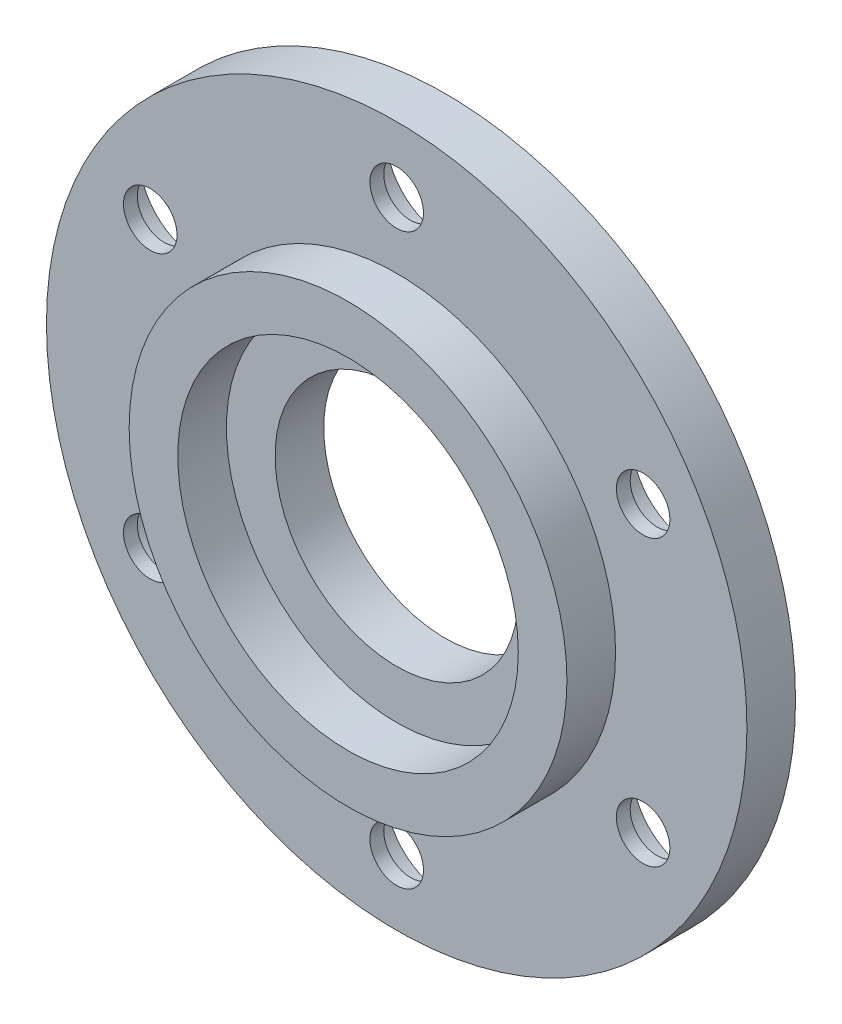
SolidWorks part; units mm, degrees
material "6061-T6 (SS)"
ref_plane "Front Plane" through (0, 0, 0) normal (0, 0, 1) x (1, 0, 0)
ref_plane "Top Plane" through (0, 0, 0) normal (0, 1, 0) x (1, 0, 0)
ref_plane "Right Plane" through (0, 0, 0) normal (1, 0, 0) x (0, 0, -1)
sketch "Sketch Spindle Skeleton" plane through (0, 0, 0) normal (1, 0, 0) x (0, 0, -1)
  line L0 (-109.9, -9.5) -> (-134, -9.5)
  line L5 (-1000, 0) -> (49000, 0)
  line L6 (0, -9.5) -> (0, 9.5)
  line L13 (0, 9.5) -> (-48.3, 9.5)
  line L26 (-48.3, 9.5) -> (-48.3, 14)
  line L27 (-48.3, 14) -> (-109.9, 14)
  line L32 (-109.9, 14) -> (-109.9, 9.5)
  line L34 (-150, 7) -> (-150, -7)
  line L36 (-109.9, -9.5) -> (-109.9, -14)
  line L37 (-109.9, -14) -> (-48.3, -14)
  line L38 (-48.3, -14) -> (-48.3, -9.5)
  line L39 (0, -9.5) -> (-48.3, -9.5)
  line L40 (-24.2, 36) -> (-19.2, 36)
  line L41 (-126.5, 22.5) -> (-109.9, 22.5)
  line L42 (-126.5, 22.5) -> (-126.5, -22.5)
  line L43 (-126.5, -22.5) -> (-109.9, -22.5)
  line L44 (-109.9, 22.5) -> (-109.9, -22.5)
  line L45 (-126.5, 22.5) -> (-109.9, -22.5) construction
  line L46 (-126.5, -22.5) -> (-109.9, 22.5) construction
  line L47 (-31.7, 22.5) -> (-48.3, 22.5)
  line L48 (-31.7, 22.5) -> (-31.7, -22.5)
  line L49 (-31.7, -22.5) -> (-48.3, -22.5)
  line L50 (-48.3, 22.5) -> (-48.3, -22.5)
  line L51 (-31.7, 22.5) -> (-48.3, -22.5) construction
  line L52 (-31.7, -22.5) -> (-48.3, 22.5) construction
  line L59 (-19.2, 36) -> (-19.2, -36)
  line L60 (-19.2, -36) -> (-24.2, -36)
  line L61 (-24.2, -22.5) -> (-29.2, -22.5)
  line L62 (-29.2, -22.5) -> (-29.2, -17.5)
  line L63 (-29.2, -17.5) -> (-24.2, -17.5)
  line L64 (-24.2, -17.5) -> (-24.2, 17.5)
  line L65 (-24.2, 17.5) -> (-29.2, 17.5)
  line L66 (-29.2, 17.5) -> (-29.2, 22.5)
  line L67 (-29.2, 22.5) -> (-24.2, 22.5)
  line L68 (-24.2, 22.5) -> (-24.2, 36)
  line L69 (-24.2, -22.5) -> (-24.2, -36)
  line L71 (-131.5, 36) -> (-25.2, 36)
  line L72 (-131.5, 36) -> (-131.5, -36)
  line L73 (-131.5, -36) -> (-25.2, -36)
  line L74 (-25.2, 36) -> (-25.2, -36)
  line L75 (-131.5, 36) -> (-25.2, -36) construction
  line L76 (-131.5, -36) -> (-25.2, 36) construction
  line L77 (-134, -9.5) -> (-134, -7)
  line L78 (-134, -7) -> (-150, -7)
  line L79 (-109.9, 9.5) -> (-134, 9.5)
  line L80 (-134, 7) -> (-150, 7)
  line L81 (-134, 9.5) -> (-134, 7)
  line L82 (-121.95, 9.5) -> (-121.95, -9.5) construction
  line L83 (-24.15, 9.5) -> (-24.15, -9.5) construction
  point P3 (0, 0)
  point P18 (-118.2, 0)
  point P24 (-40, 0)
  point P29 (-78.35, 0)
  point P48 (-19.2, 29.25)
revolve "Main Revolve" add sketch "Sketch Spindle Skeleton" angle 360 about L5 region at (0, 22.65, 21.8091) region at (0, 20, 27.2)
sketch "Sketch Center Cut" plane through (0, 0, 24.2) normal (0, 0, 1) x (1, 0, 0)
  circle A0 centre (0, 0) radius 17.5 construction
  circle A1 centre (0, 0) radius 17.5 construction
  circle A2 centre (0, 0) radius 12.5
  dimension "D1" = 5
extrude "Cut Center" cut sketch "Sketch Center Cut" against normal through all
hole_wizard "CBORE for M5 Hex Head Bolt1" positions "Hole wizard sketch 1" profile "Hole wizard sketch 2" counterbore size "M5" standard "ANSI Metric" end condition through all
sketch "Hole wizard sketch 1" plane through (0, 0, 19.2) normal (0, 0, -1) x (-1, 0, 0)
  point P0 (0, 29.25)
sketch "Hole wizard sketch 2" plane through (0, 29.25, 19.2) normal (1, 0, 0) x (0, 1, 0)
  line L0 (0, 0) -> (0, 10)
  line L1 (0, 10) -> (2.75, 10)
  line L3 (2.75, 10) -> (2.75, 3.58)
  line L4 (2.75, 3.58) -> (6.12, 3.58)
  line L5 (6.12, 3.58) -> (6.12, 0)
  line L7 (6.12, 0) -> (0, 0)
  line L11 (0, -6.35) -> (0, 107.95) construction
  dimension "Thru Hole Dia." = 5.5
  dimension "Thru Hole Depth" = 10
  dimension "C'Bore Dia." = 12.24
  dimension "C'Bore Depth" = 3.58
pattern_circular "CirPattern1" count 6 over 360 about axis through (0, 0, 19.2) along (0, 0, 1) of "CBORE for M5 Hex Head Bolt1"
